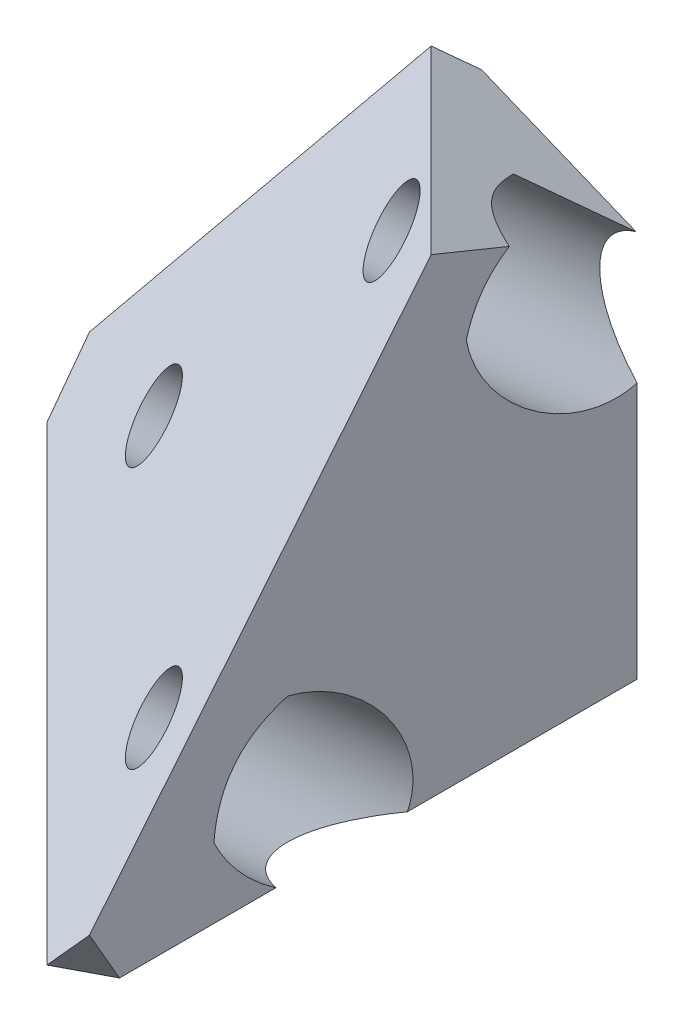
SolidWorks part; units mm, degrees
ref_plane "Front Plane" through (0, 0, 0) normal (0, 0, 1) x (1, 0, 0)
ref_plane "Top Plane" through (0, 0, 0) normal (0, 1, 0) x (1, 0, 0)
ref_plane "Right Plane" through (0, 0, 0) normal (1, 0, 0) x (0, 0, -1)
sketch "Sketch1" plane through (0, 0, 0) normal (0, 1, 0) x (1, 0, 0)
  line L0 (-7.7782, 7.7782) -> (7.7782, -7.7782)
  line L1 (-7.7782, 7.7782) -> (7.7782, 7.7782)
  line L2 (7.7782, 7.7782) -> (7.7782, -7.7782)
  dimension "D1" = 22
extrude "Boss-Extrude1" add sketch "Sketch1" along normal blind 14
ref_plane "Plane1" through (0, 0, 0) normal (-0.7071, 0, -0.7071) x (0, -1, 0)
sketch "Sketch2" plane through (0, 0, 0) normal (-0.7071, 0, -0.7071) x (0, -1, 0)
  line L0 (0, 0) -> (-14, -8.0829)
  line L1 (-14, -8.0829) -> (-14, 0)
  line L2 (-14, 0) -> (0, 0)
  dimension "D1" = 30
extrude "Cut-Extrude1" cut sketch "Sketch2" against normal through all both and the other way through all
ref_plane "Plane2" through (7.3485, -6, -7.3485) normal (-0.6124, 0.5, 0.6124) x (0.7906, 0.3873, 0.4743)
sketch "Sketch7" plane through (0, 0, -7.7782) normal (0, 0, -1) x (-1, 0, 0)
  line L4 (-7.7782, 0) -> (7.7782, 0)
  line L5 (7.7782, 0) -> (-3.6528, 14)
  line L6 (-3.6528, 14) -> (-7.7782, 14)
  line L7 (-7.7782, 14) -> (-7.7782, 0)
  line L8 (-7.7782, 0) -> (7.7782, 0)
  line L9 (7.7782, 0) -> (-3.6528, 14)
  line L10 (-3.6528, 14) -> (-7.7782, 14)
  line L11 (-7.7782, 14) -> (-7.7782, 0)
  dimension "D1" = 0
extrude "Boss-Extrude2" add sketch "Sketch7" along normal blind 2
hole_wizard "CSK for M2 Flat Head Machine Screw1" positions "Sketch3" profile "Sketch4" countersink size "M2" standard "ANSI Metric"
sketch "Sketch3" plane through (7.3485, -6, -7.3485) normal (-0.6124, 0.5, 0.6124) x (0.7906, 0.3873, 0.4743)
  line L1 (7.2296, 14.4591) -> (2.4597, 4.9193) construction
  line L2 (6.9318, 1.5652) -> (-2.9069, 6.4846) construction
  line L4 (-9.8387, 4.9193) -> (9.8387, -4.9193) construction
  line L5 (9.8387, 13.1546) -> (4.6204, 15.7637) construction
  point P0 (6.9318, 1.5652)
  point P4 (6.4846, 12.9692)
  point P12 (-2.9069, 6.4846)
  dimension "D1" = 5.5
  dimension "D2" = 10
  dimension "D3" = 4.5
sketch "Sketch4" plane through (12.8285, -2.1029, -5.0504) normal (0.7891, 0.4344, 0.4344) x (-0.0488, 0.7492, -0.6605)
  line L0 (0, 0) -> (0, 13.921)
  line L1 (0, 13.921) -> (1.2, 13.2)
  line L2 (1.2, 13.2) -> (1.2, 11)
  line L3 (1.2, 11) -> (2.2, 10)
  line L4 (2.2, 10) -> (2.2, 0)
  line L6 (2.2, 0) -> (0, 0)
  line L7 (-1.2, 11) -> (-2.2, 10) construction
  line L10 (0, 13.921) -> (-1.2, 13.2) construction
  line L11 (0, -6.35) -> (0, 107.95) construction
  dimension "Hole Dia." = 2.4
  dimension "Hole Depth" = 13.2
  dimension "C'Sink Dia." = 4.4
  dimension "C'Sink Angle" = 90
  dimension "Drill Angle" = 118
  dimension "Head Clearance" = 10
hole_wizard "M2x0.4 Tapped Hole1" positions "Sketch5" profile "Sketch6" tap size "M2x0.4" standard "ANSI Metric"
sketch "Sketch5" plane through (0, 0, -9.7782) normal (0, 0, -1) x (-1, 0, 0)
  line L2 (-7.7782, 7.6299) -> (-7.7782, 0) construction
  line L3 (0.5668, 0) -> (7.7782, 0) construction
  point P0 (-2.7782, 9.5)
  point P2 (-5.7782, 1.5)
  point P4 (3.7218, 1.5)
  dimension "D1" = 1.5
  dimension "D2" = 2
  dimension "D3" = 8
  dimension "D4" = 3
  dimension "D5" = 9.5
sketch "Sketch6" plane through (2.7782, 9.5, -9.7782) normal (1, 0, 0) x (0, 1, 0)
  line L0 (0, 0) -> (0, 3.9807)
  line L1 (0, 3.9807) -> (0.8, 3.5)
  line L2 (0.8, 3.5) -> (0.8, 0.225)
  line L3 (0.8, 0.225) -> (1.025, 0)
  line L5 (1.025, 0) -> (0, 0)
  line L6 (-0.8, 0.225) -> (-1.025, 0) construction
  line L10 (0, 3.9807) -> (-0.8, 3.5) construction
  line L11 (0, -6.35) -> (0, 107.95) construction
  dimension "Tap Drill Dia." = 1.6
  dimension "Tap Drill Depth" = 3.5
  dimension "Near C'Sink Dia." = 2.05
  dimension "Near C'Sink Angle" = 90
  dimension "Drill Angle" = 118
cosmetic thread "Hole Thread1" parameters "D1"=3, "D2"=2
cosmetic thread "Hole Thread3" parameters "D1"=3, "D2"=2
cosmetic thread "Hole Thread4" parameters "D1"=3, "D2"=2
sketch "Sketch11" plane through (0, 0, 0) normal (-0.6124, 0.5, 0.6124) x (0.4743, -0.3873, 0.7906)
  line L4 (-4.6204, 15.7637) -> (-9.463, 15.7637)
  line L5 (-9.463, 15.7637) -> (-11.4198, 13.1546)
  line L6 (-11.4198, 13.1546) -> (-9.8387, 13.1546)
  line L7 (-9.8387, 13.1546) -> (-4.6204, 15.7637)
  line L8 (-4.6204, 15.7637) -> (-9.463, 15.7637)
  line L9 (-9.463, 15.7637) -> (-11.4198, 13.1546)
  line L10 (-11.4198, 13.1546) -> (-9.8387, 13.1546)
  line L11 (-9.8387, 13.1546) -> (-4.6204, 15.7637)
  dimension "D1" = 0
extrude "Boss-Extrude4" [suppressed] add sketch "Sketch11" against normal up to surface (1.2247 mm away) up to face at (5.7155, 14, -7.7468)
sketch "Sketch12" plane through (0, 0, 0) normal (-0.6124, 0.5, 0.6124) x (0.4743, -0.3873, 0.7906)
  line L4 (-9.8387, -4.9193) -> (-9.8387, 13.1546)
  line L5 (-9.8387, 13.1546) -> (-11.4198, 13.1546)
  line L6 (-11.4198, 13.1546) -> (-11.4198, -4.9193)
  line L7 (-11.4198, -4.9193) -> (-9.8387, -4.9193)
  line L8 (-9.8387, -4.9193) -> (-9.8387, 13.1546)
  line L9 (-9.8387, 13.1546) -> (-11.4198, 13.1546)
  line L10 (-11.4198, 13.1546) -> (-11.4198, -4.9193)
  line L11 (-11.4198, -4.9193) -> (-9.8387, -4.9193)
  dimension "D1" = 0
extrude "Boss-Extrude5" add sketch "Sketch12" against normal up to surface (1.2247 mm away) up to face at (-2.0627, 7, -8.7782)
sketch "Sketch9" plane through (0, 0, 0) normal (-0.6124, 0.5, 0.6124) x (0.4743, -0.3873, 0.7906)
  line L0 (8.2387, 6.1193) -> (8.0498, 4.0249)
  line L1 (-4.6204, 15.7637) -> (9.8387, 4.9193) construction
  line L2 (-9.8387, -4.9193) -> (9.8387, 4.9193) construction
  line L3 (8.0498, 4.0249) -> (9.8387, 4.9193)
  line L4 (9.8387, 4.9193) -> (8.2387, 6.1193)
  line L5 (-9.631, -4.8155) -> (-11.4198, -5.7099)
  line L6 (-11.4198, -5.7099) -> (-11.4198, -3.7099)
  line L7 (-11.4198, -3.7099) -> (-9.631, -4.8155)
  line L8 (-9.631, -4.8155) -> (-9.9137, -4.963)
  line L10 (-11.4198, 13.1546) -> (-11.4198, -4.9193) construction
  line L11 (-4.6204, 15.7637) -> (-11.4198, 12.364)
  line L12 (-11.4198, 12.364) -> (-11.4198, 20.8633)
  line L13 (-11.4198, 20.8633) -> (-4.6204, 15.7637)
  line L14 (-4.6204, 15.7637) -> (-9.8387, 13.1546) construction
  dimension "D1" = 2
extrude "Cut-Extrude3" cut sketch "Sketch9" against normal through all both and the other way through all contours L5 L6 L7 | L0 L3 L4 | L12 L13 L11
